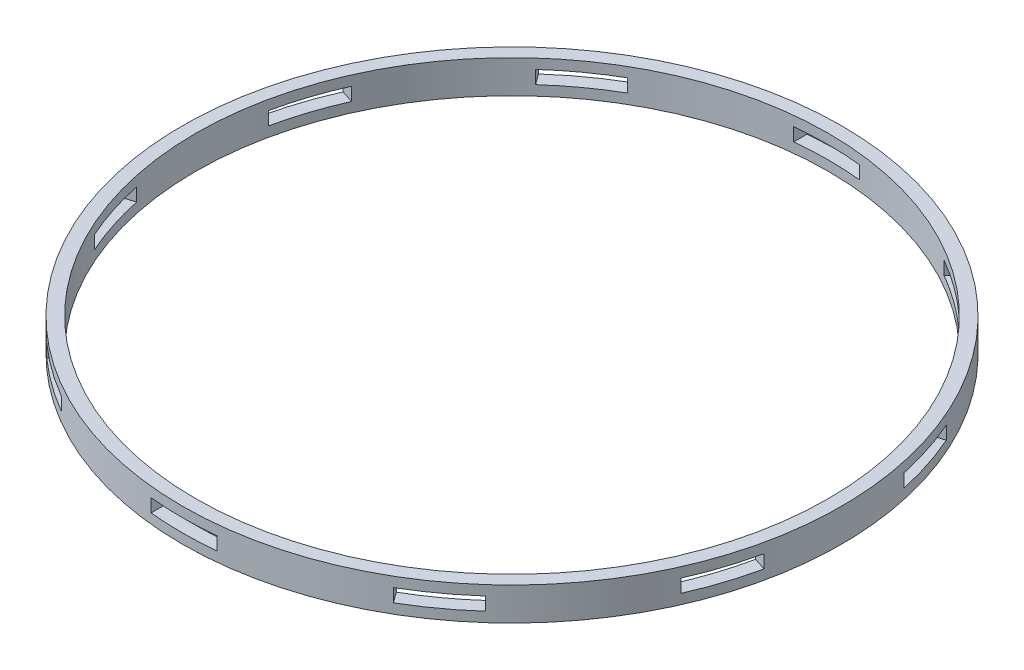
SolidWorks part; units mm, degrees
ref_plane "Front Plane" through (0, 0, 0) normal (0, 0, 1) x (1, 0, 0)
ref_plane "Top Plane" through (0, 0, 0) normal (0, 1, 0) x (1, 0, 0)
ref_plane "Right Plane" through (0, 0, 0) normal (1, 0, 0) x (0, 0, -1)
sketch "Sketch1" plane through (0, 0, 0) normal (0, 1, 0) x (1, 0, 0)
  line L0 (40.8443, 86.8778) -> (42.5461, 90.4977) construction
  circle A0 centre (0, 0) radius 96
  circle A1 centre (0, 0) radius 100
  dimension "D2" = 192
  dimension "D1" = 4
extrude "Boss-Extrude1" add sketch "Sketch1" along normal blind 10
sketch "Sketch2" plane through (0, 0, 0) normal (0, 0, 1) x (1, 0, 0)
  line L0 (-100, 0) -> (100, 0) construction
  line L1 (-10, 7) -> (10, 7)
  line L2 (-10, 7) -> (-10, 3)
  line L3 (-10, 3) -> (10, 3)
  line L4 (10, 7) -> (10, 3)
  line L5 (96, 10) -> (-96, 10) construction
  point P11 (0, 3)
  dimension "D1" = 3
  dimension "D2" = 3
  dimension "D3" = 20
extrude "Cut-Extrude1" cut sketch "Sketch2" against normal through all
ref_axis "Axis1" through (0, 10, 0) along (0, -1, 0)
pattern_circular "CirPattern1" count 10 over 360 about axis through (0, 10, 0) along (0, -1, 0) of "Cut-Extrude1"
